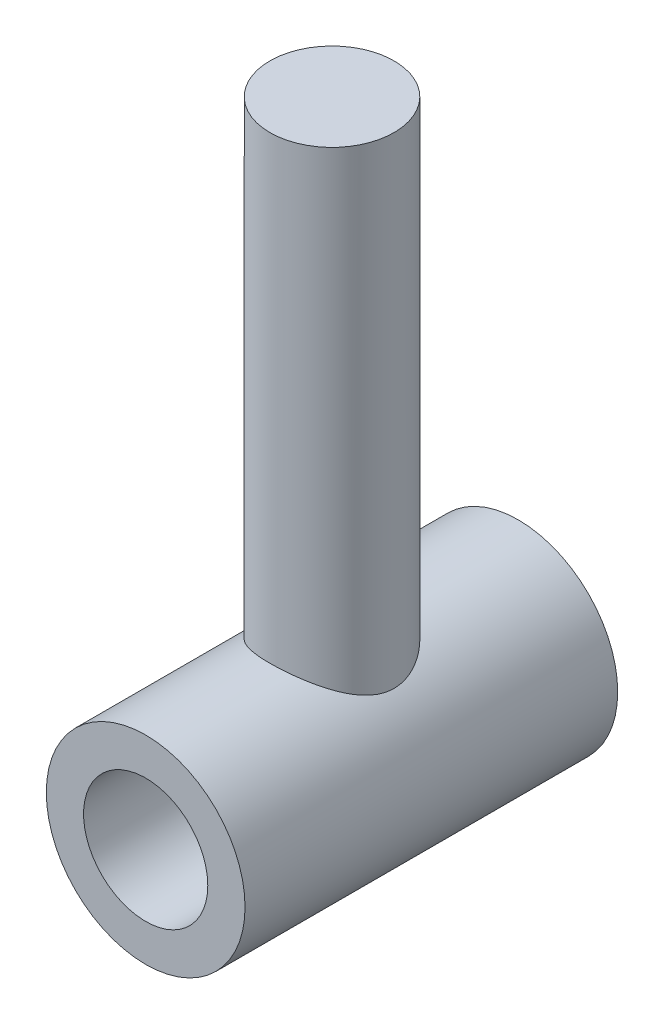
SolidWorks part; units mm, degrees
ref_plane "Front Plane" through (0, 0, 0) normal (0, 0, 1) x (1, 0, 0)
ref_plane "Top Plane" through (0, 0, 0) normal (0, 1, 0) x (1, 0, 0)
ref_plane "Right Plane" through (0, 0, 0) normal (1, 0, 0) x (0, 0, -1)
sketch "Sketch1" plane through (0, 0, 0) normal (0, 0, 1) x (1, 0, 0)
  circle A0 centre (0, 0) radius 5
  dimension "D1" = 10
extrude "Extrude-Thin1" add sketch "Sketch1" along normal mid plane 30 thin thin type one direction wall 3
sketch "Sketch2" plane through (0, 0, 0) normal (0, 1, 0) x (1, 0, 0)
  circle A0 centre (0, 0) radius 5
  dimension "D1" = 10
extrude "Boss-Extrude1" add sketch "Sketch2" against normal up to surface (37 mm away) from offset 45 up to face at (8, 0, 15)
